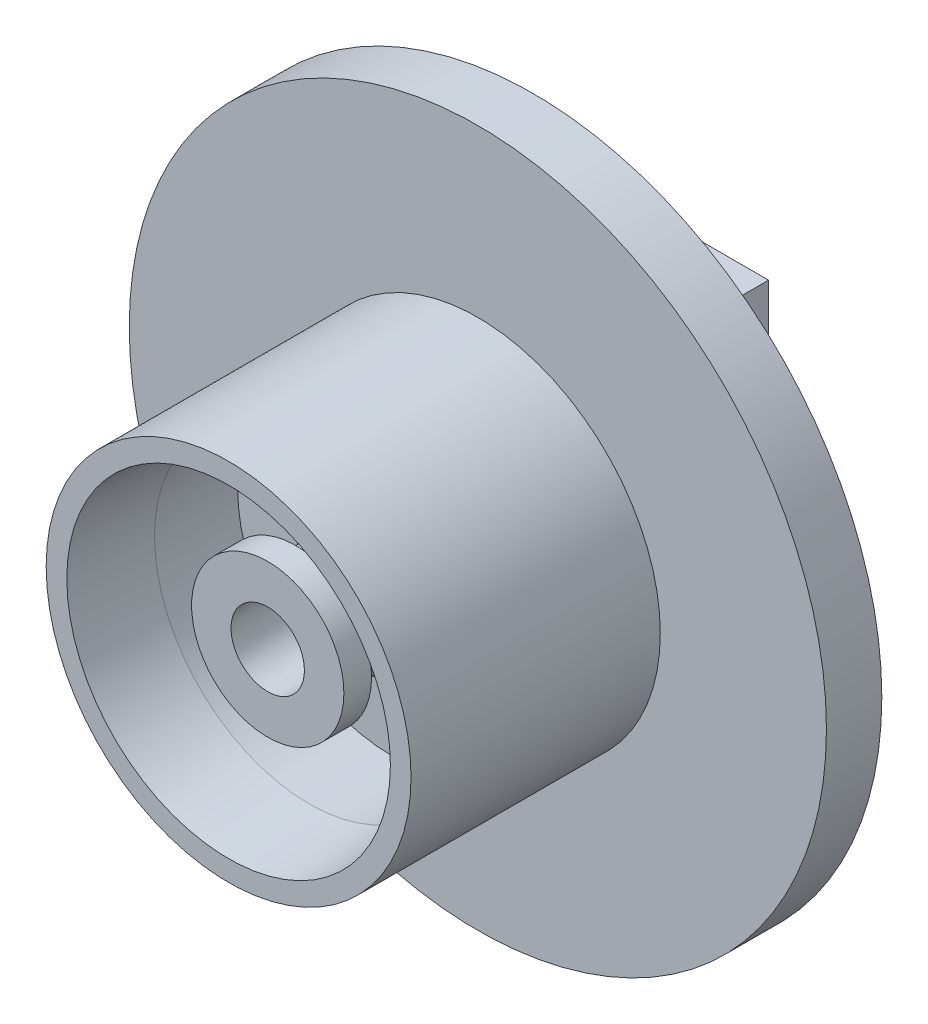
SolidWorks part; units mm, degrees
ref_plane "Front Plane" through (0, 0, 0) normal (0, 0, 1) x (1, 0, 0)
ref_plane "Top Plane" through (0, 0, 0) normal (0, 1, 0) x (1, 0, 0)
ref_plane "Right Plane" through (0, 0, 0) normal (1, 0, 0) x (0, 0, -1)
sketch "Sketch2" plane through (0, 0, 0) normal (0, 1, 0) x (1, 0, 0)
  line L0 (0, 0) -> (0, -41.7419) construction
  line L1 (11.175, 0) -> (11.175, -5)
  line L2 (11.175, -5) -> (7, -9.175)
  line L3 (7, -9.175) -> (7, -10.175)
  line L4 (7, -10.175) -> (11.175, -10.175)
  line L5 (11.175, -10.175) -> (11.175, -16.175)
  line L6 (11.6846, -22) -> (13.175, -22)
  line L7 (13.175, -22) -> (13.175, -4)
  line L8 (13.175, -4) -> (25.175, -4)
  line L9 (25.175, -4) -> (25.175, 0)
  line L10 (25.175, 0) -> (11.175, 0)
  line L11 (11.175, -16.175) -> (11.6846, -22)
  dimension "D1" = 11.175
  dimension "D2" = 12
  dimension "D3" = 2
  dimension "D4" = 5
  dimension "D5" = 135
  dimension "D6" = 7
  dimension "D7" = 4
  dimension "D8" = 22
  dimension "D9" = 1
  dimension "D10" = 6
  dimension "D11" = 5
revolve "Revolve1" add sketch "Sketch2" angle 360 about L0
ref_plane "Plane1" through (0, 0, 5) normal (0, 0, -1) x (-1, 0, 0)
ref_plane "Plane2" through (0, 0, -2) normal (0, 0, -1) x (-1, 0, 0)
sketch "Sketch3" plane through (0, 0, -2) normal (0, 0, -1) x (-1, 0, 0)
  line L1 (-10, -15) -> (10, -15)
  line L2 (-10, -15) -> (-10, 15)
  line L3 (-10, 15) -> (10, 15)
  line L4 (10, -15) -> (10, 15)
  line L5 (-10, -15) -> (10, 15) construction
  line L6 (-10, 15) -> (10, -15) construction
  circle A2 centre (0, 0) radius 5.5
  circle A4 centre (0, 0) radius 2.65
  circle A5 centre (0, 0) radius 3.875
  point P0 (0, 0)
  dimension "D2" = 30
  dimension "D3" = 5.3
  dimension "D4" = 7.75
  dimension "D5" = 11
  dimension "D1" = 20
extrude "Boss-Extrude1" add sketch "Sketch3" along normal blind 4 from offset 1 separate body contours L3 L4 L1 L2 | A4
extrude "Boss-Extrude3" add sketch "Sketch3<4>" against normal blind 10 from surface contours A5 A4 region at (3.7654, 0, -2) starting at face at (0, 0, -3)
sketch "Sketch3<4>" plane through (0, 0, -2) normal (0, 0, -1) x (-1, 0, 0) same geometry as "Sketch3"
extrude "Boss-Extrude4" add sketch "Sketch3<5>" along normal up to surface (1 mm away) contours A2 A5 region at (5.3444, 0, -2) up to face at (0, 0, -3)
sketch "Sketch3<5>" plane through (0, 0, -2) normal (0, 0, -1) x (-1, 0, 0) same geometry as "Sketch3"
ref_plane "Plane3" through (0, 0, 17.175) normal (0, 0, 1) x (1, 0, 0)
sketch "Sketch4" plane through (0, 0, 17.175) normal (0, 0, 1) x (1, 0, 0)
  circle A0 centre (0, 0) radius 5.5 construction
  circle A1 centre (0, 0) radius 3.875 construction
  circle A2 centre (0, 0) radius 2.65 construction
  circle A3 centre (0, 0) radius 5.5
  circle A4 centre (0, 0) radius 3.875
  circle A5 centre (0, 0) radius 2.65
extrude "Boss-Extrude5" add sketch "Sketch4" against normal offset from surface (9.775 mm away) 0.4 separate body contours A4 A5 region at (-3.7654, 0, 17.175) up to face at (3.875, 0, 7)
extrude "Boss-Extrude6" add sketch "Sketch4<3>" along normal blind 2 contours A3 A4 | A4 A5 region at (-5.3444, 0, 17.175) region at (-3.7654, 0, 17.175)
sketch "Sketch4<3>" plane through (0, 0, 17.175) normal (0, 0, 1) x (1, 0, 0) same geometry as "Sketch4"
